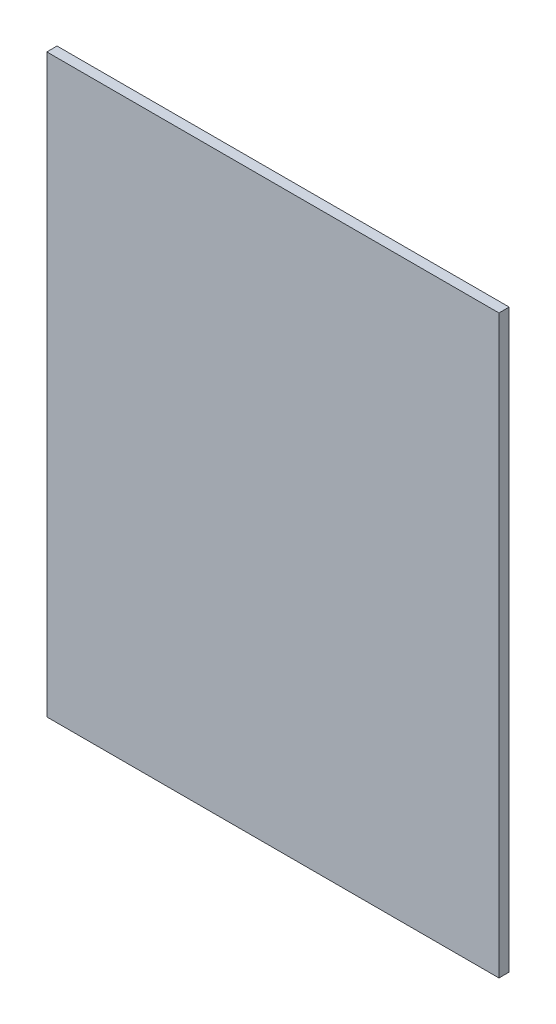
SolidWorks part; units mm, degrees
ref_plane "Front Plane" through (0, 0, 0) normal (0, 0, 1) x (1, 0, 0)
ref_plane "Top Plane" through (0, 0, 0) normal (0, 1, 0) x (1, 0, 0)
ref_plane "Right Plane" through (0, 0, 0) normal (1, 0, 0) x (0, 0, -1)
sketch "Sketch1" plane through (0, 0, 0) normal (0, 0, 1) x (1, 0, 0)
  line L1 (-28.0807, 65.0107) -> (55.9193, 65.0107)
  line L2 (-28.0807, 65.0107) -> (-28.0807, -41.9893)
  line L3 (-28.0807, -41.9893) -> (55.9193, -41.9893)
  line L4 (55.9193, 65.0107) -> (55.9193, -41.9893)
  dimension "D1" = 84
  dimension "D2" = 107
base flange "Base-Flange1" sketch "Sketch1" thickness 1.8974 reverse thickness direction no parameters "D1"=2.54
sketch "Bend-Lines1" plane through (0, 0, 0) normal (0, 1, 0) x (1, 0, 0)
sketch "Bounding-Box1" plane through (0, 0, 0) normal (0, 1, 0) x (1, 0, 0)
sheet metal parameters "Sheet-Metal1" thickness 1.8974 parameters "D1"=2.54
flat pattern "Flat-Pattern1" [suppressed]
sketch "Bend-Lines2" plane through (0, 0, 0) normal (0, 1, 0) x (1, 0, 0)
sketch "Bounding-Box2" [suppressed] plane through (0, 0, 0) normal (0, 1, 0) x (1, 0, 0)
